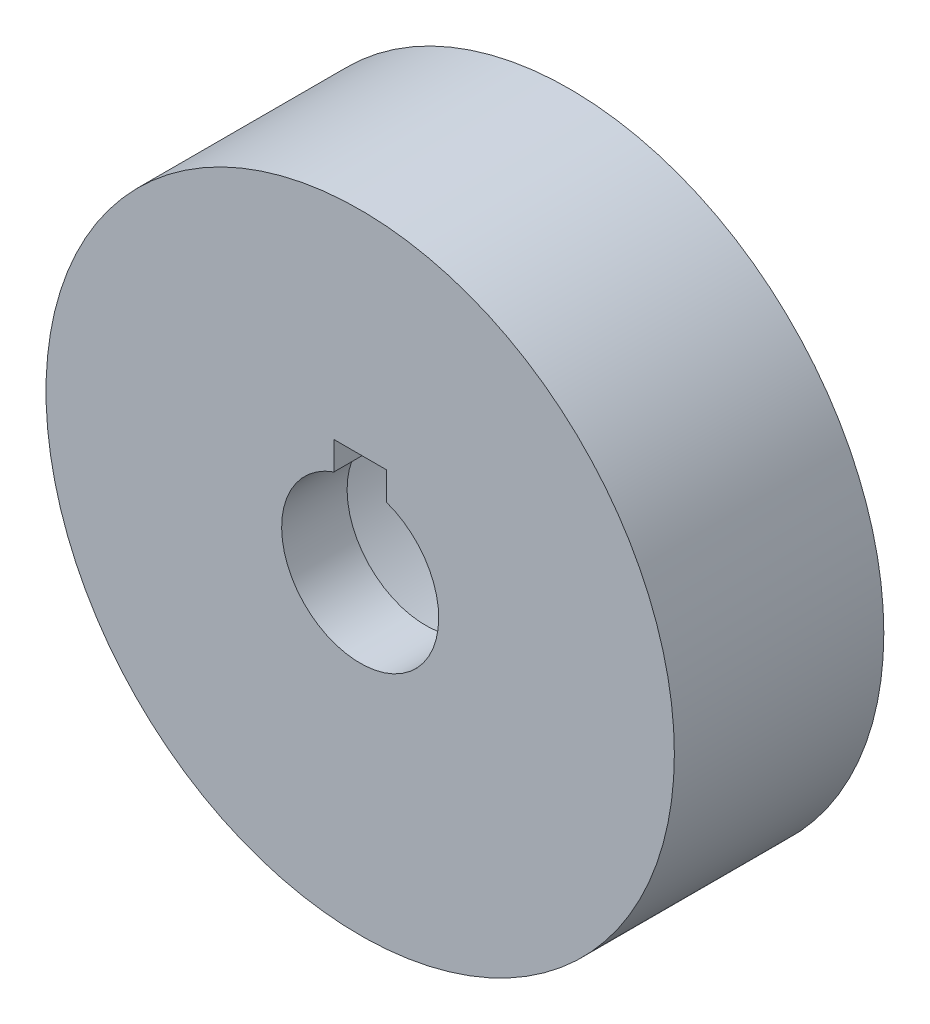
SolidWorks part; units mm, degrees
ref_plane "Front Plane" through (0, 0, 0) normal (0, 0, 1) x (1, 0, 0)
ref_plane "Top Plane" through (0, 0, 0) normal (0, 1, 0) x (1, 0, 0)
ref_plane "Right Plane" through (0, 0, 0) normal (1, 0, 0) x (0, 0, -1)
sketch "Sketch1" plane through (0, 0, 0) normal (0, 0, 1) x (1, 0, 0)
  line L0 (0, 6) -> (0, 7.8) construction
  line L1 (-2, 7.8) -> (2, 7.8)
  line L2 (-2, 7.8) -> (-2, 5.6569)
  line L3 (2, 7.8) -> (2, 5.6569)
  line L4 (0, 0) -> (-10.01, 0) construction
  line L10 (-10.01, 0) -> (-10.01, 7) construction
  line L11 (-12.76, 7) -> (-7.26, 7) construction
  line L26 (-12.76, 7) -> (-12.76, 3) construction
  line L27 (-12.76, 3) -> (-7.26, 3) construction
  line L28 (-7.26, 3) -> (-7.26, 7) construction
  line L30 (-10.01, 3) -> (-10.01, -9) construction
  line L31 (-12.01, -9) -> (-8.01, -9) construction
  line L32 (-12.01, -9) -> (-12.01, 3) construction
  line L33 (-8.01, -9) -> (-8.01, 3) construction
  circle A0 centre (0, 0) radius 6
  circle A1 centre (0, 0) radius 14 construction
  circle A2 centre (0, 0) radius 24
  circle A7 centre (0, 0) radius 15.5
  point P8 (0, 7.8)
  point P17 (-10.01, 7)
  point P18 (-10.01, 7)
  point P27 (-10.01, -9)
  point P30 (-10.01, 3)
  point P38 (-10.01, 3)
  dimension "D1" = 12
  dimension "D4" = 28
  dimension "D5" = 10
  dimension "D12" = 31
  dimension "D2" = 1.8
  dimension "D3" = 4
  dimension "D6" = 10.01
  dimension "D7" = 5.5
  dimension "D8" = 3
  dimension "D9" = 4
  dimension "D10" = 12
  dimension "D11" = 4
extrude "Boss-Extrude1" add sketch "Sketch1" along normal blind 5 contours A2 A1 | A1 A0 L2 L1 L3 | A1 | A1 | A1 | A1 | A1 | A1 | A1 | A1 region at (-23.3212, 0, 0) region at (-15.0616, 0, 0)
extrude "Boss-Extrude2" add sketch "Sketch1<3>" against normal blind 11 contours A2 A1 region at (-23.3212, 0, 0)
sketch "Sketch1<3>" plane through (0, 0, 0) normal (0, 0, 1) x (1, 0, 0) same geometry as "Sketch1"
sketch "Sketch2" plane through (0, 0, -11) normal (0, 0, -1) x (-1, 0, 0)
  line L0 (0, 0) -> (0, -24) construction
  line L2 (15.5, 0) -> (24, 0) construction
  circle A8 centre (0, 0) radius 24 construction
  circle A9 centre (0, 0) radius 15.5 construction
  point P7 (0, -19.75)
  point P58 (19.75, 0)
  point P59 (0, 19.75)
  point P60 (-19.75, 0)
  point P84 (19.75, 0)
  dimension "D1" = 4
hole_wizard "Tap Drill for M5x0.8 Tap1" positions "Sketch2" profile "Sketch3" hole size "M5x0.8" standard "ANSI Metric"
sketch "Sketch3" plane through (19.75, 0, -11) normal (1, 0, 0) x (0, 1, 0)
  line L0 (0, 0) -> (0, 11.2618)
  line L1 (0, 11.2618) -> (2.1, 10)
  line L2 (2.1, 10) -> (2.1, 0)
  line L5 (2.1, 0) -> (0, 0)
  line L10 (0, 11.2618) -> (-2.1, 10) construction
  line L11 (0, -6.35) -> (0, 107.95) construction
  dimension "Hole Dia." = 4.2
  dimension "Hole Depth" = 10
  dimension "Drill Angle" = 118
